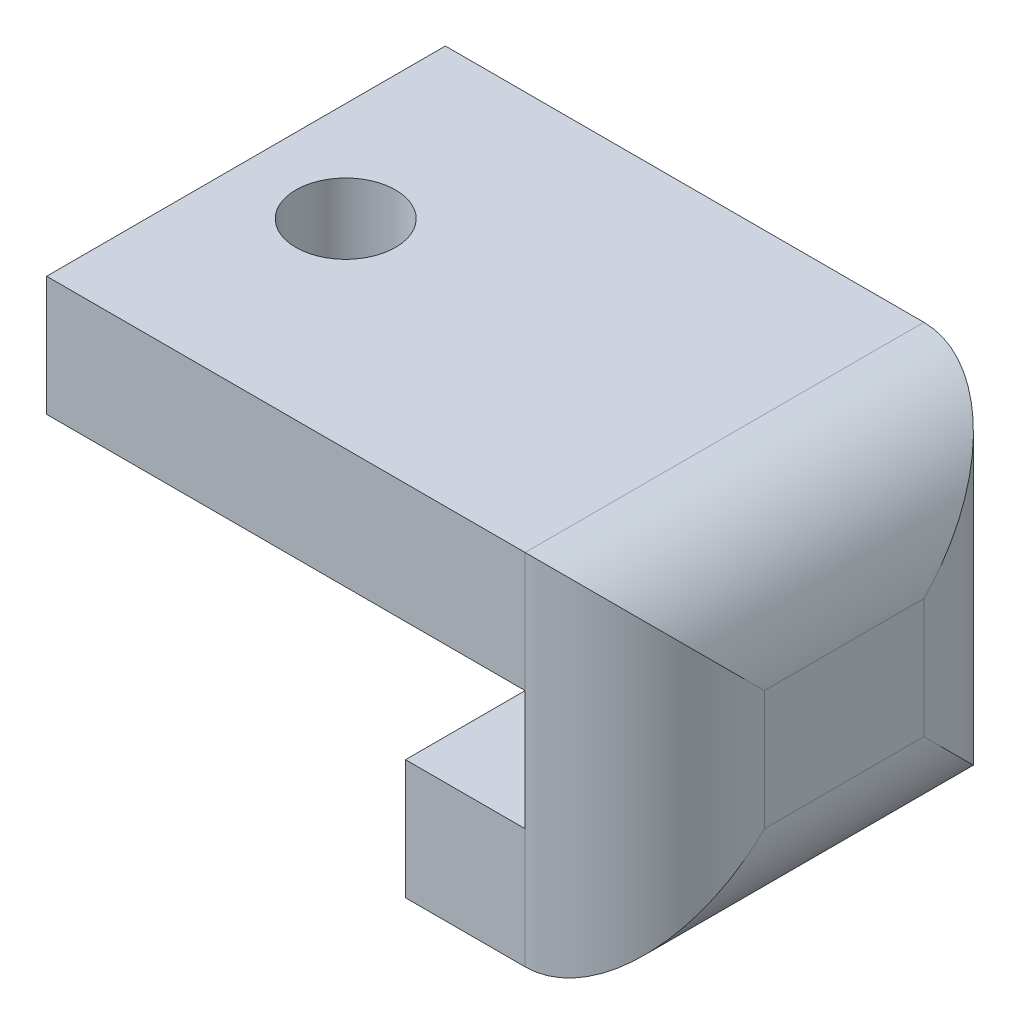
SolidWorks part; units mm, degrees
material "ABS generico"
ref_plane "Piano frontale" through (0, 0, 0) normal (0, 0, 1) x (1, 0, 0)
ref_plane "Piano superiore" through (0, 0, 0) normal (0, 1, 0) x (1, 0, 0)
ref_plane "Piano destro" through (0, 0, 0) normal (1, 0, 0) x (0, 0, -1)
sketch "Schizzo1" plane through (0, 0, 0) normal (0, 0, 1) x (1, 0, 0)
  line L0 (-6, 0) -> (6, 0)
  line L1 (6, 0) -> (6, -3)
  line L2 (6, -3) -> (3, -3)
  line L3 (3, -3) -> (3, -6)
  line L4 (3, -6) -> (9, -6)
  line L5 (9, -6) -> (9, 3)
  line L6 (9, 3) -> (-6, 3)
  line L7 (-6, 3) -> (-6, 0)
  dimension "D1" = 15
  dimension "D2" = 3
  dimension "D3" = 3
  dimension "D4" = 3
  dimension "D5" = 3
  dimension "D6" = 9
  dimension "D7" = 6
extrude "Estrusione-Estrusione1" add sketch "Schizzo1" along normal blind 10
fillet "Raccordo1" radius 3 4 edges at (9, -6, 5) (9, -1.5, 10) (9, 3, 5) (9, -1.5, 0)
hole_wizard "Foro filettato M3x0.5-1" positions "Schizzo3" profile "Schizzo2" tap size "M3x0.5" standard "Ansi Metric" end condition through all
sketch "Schizzo3" plane through (0, 3, 0) normal (0, 1, 0) x (1, 0, 0)
  line L0 (-3.5, -5) -> (-6, -5) construction
  line L1 (-6, -10) -> (-6, 0) construction
  line L3 (-3.5, -5) -> (-3.5, 0) construction
  line L4 (6, 0) -> (-6, 0) construction
  line L6 (-3.5, -5) -> (-3.5, -10) construction
  line L7 (6, -10) -> (-6, -10) construction
  point P0 (-3.5, -5)
  dimension "D1" = 2.5
sketch "Schizzo2" plane through (-3.5, 3, 5) normal (1, 0, 0) x (0, 0, 1)
  line L0 (0, 0) -> (0, 9)
  line L1 (0, 9) -> (1.25, 9)
  line L2 (1.25, 9) -> (1.25, 0)
  line L5 (1.25, 0) -> (0, 0)
  line L11 (0, -6.35) -> (0, 107.95) construction
  dimension "Thru Tap Drill Dia." = 2.5
  dimension "Thru Tap Drill Depth" = 9
cosmetic thread "Filettatura del foro1" parameters "D2"=3
